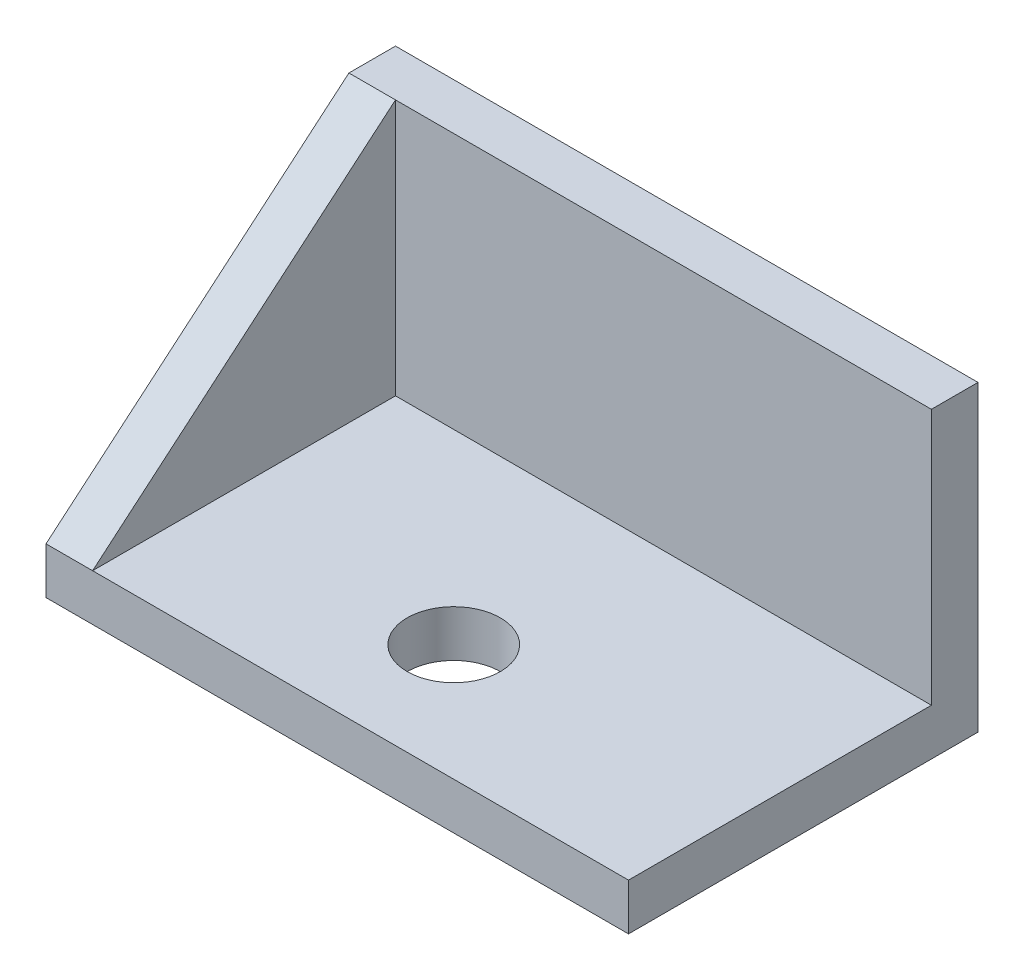
SolidWorks part; units mm, degrees
ref_plane "Front Plane" through (0, 0, 0) normal (0, 0, 1) x (1, 0, 0)
ref_plane "Top Plane" through (0, 0, 0) normal (0, 1, 0) x (1, 0, 0)
ref_plane "Right Plane" through (0, 0, 0) normal (1, 0, 0) x (0, 0, -1)
sketch "Sketch1" plane through (0, 0, 0) normal (0, 1, 0) x (1, 0, 0)
  line L0 (0, -10) -> (125, -10)
  line L1 (0, 0) -> (125, 0)
  line L2 (0, 0) -> (0, -75)
  line L3 (0, -75) -> (125, -75)
  line L4 (125, 0) -> (125, -75)
  line L5 (10, -10) -> (10, -75)
  circle A0 centre (62.5, -50) radius 10
  dimension "D5" = 20
  dimension "D1" = 75
  dimension "D2" = 125
  dimension "D3" = 10
  dimension "D4" = 10
  dimension "D6" = 62.5
  dimension "D7" = 25
extrude "Boss-Extrude1" add sketch "Sketch1" along normal mid plane 10 contours L0 L5 L3 L4 A0 | L5 L0 L2 L3 | L4 L1 L2 L0 region at (62.5, 0, 5) region at (5, 0, 42.5) region at (67.5, 0, 11.321)
extrude "Boss-Extrude2" add sketch "Sketch1<3>" along normal blind 55 from surface contours L4 L1 L2 L0 region at (62.5, 0, 5) starting at face at (62.5, 5, 60)
sketch "Sketch1<3>" plane through (0, 0, 0) normal (0, 1, 0) x (1, 0, 0) same geometry as "Sketch1"
sketch "Sketch2" plane through (0, 0, 0) normal (1, 0, 0) x (0, 0, -1)
  line L0 (-75, 5) -> (-10, 60)
  line L1 (-75, 5) -> (-10, 5)
  line L2 (-10, 5) -> (-10, 60)
extrude "Boss-Extrude3" add sketch "Sketch2" along normal blind 10
